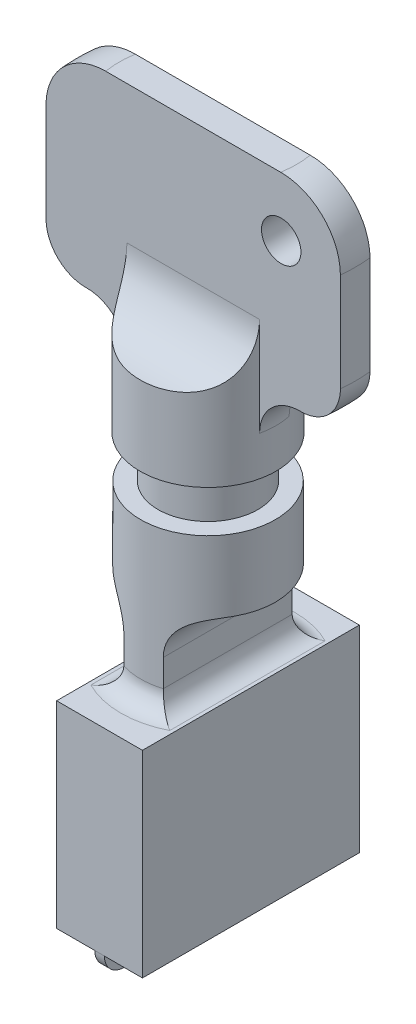
SolidWorks part; units mm, degrees
ref_plane "Front Plane" through (0, 0, 0) normal (0, 0, 1) x (1, 0, 0)
ref_plane "Top Plane" through (0, 0, 0) normal (0, 1, 0) x (1, 0, 0)
ref_plane "Right Plane" through (0, 0, 0) normal (1, 0, 0) x (0, 0, -1)
sketch "Sketch1" plane through (0, 0, 0) normal (0, 0, 1) x (1, 0, 0)
  line L0 (-3.4489, 37.7658) -> (-3.4489, 33.7658)
  line L1 (-3.4489, 33.7658) -> (-2.5348, 33.7658)
  line L2 (-2.5348, 33.7658) -> (-2.5348, 31.625)
  line L3 (-2.5348, 31.625) -> (-3.4177, 31.625)
  line L4 (-3.4177, 31.625) -> (-3.4177, 23)
  line L5 (-3.4177, 23) -> (0, 23)
  line L6 (-3.4489, 37.7658) -> (0, 37.7658)
  line L7 (0, 37.7658) -> (0, 23)
  dimension "D1" = 33.7658
  dimension "D2" = 2.1409
  dimension "D3" = 23
  dimension "D4" = 4
revolve "Revolve1" add sketch "Sketch1" angle 360 about L7
sketch "Sketch2" plane through (0, 37.7658, 0) normal (0, 1, 0) x (1, 0, 0)
  line L1 (-11.4046, 0.75) -> (11.4046, 0.75)
  line L2 (-11.4046, 0.75) -> (-11.4046, -0.75)
  line L3 (-11.4046, -0.75) -> (11.4046, -0.75)
  line L4 (11.4046, 0.75) -> (11.4046, -0.75)
  line L5 (-11.4046, 0.75) -> (11.4046, -0.75) construction
  line L6 (-11.4046, -0.75) -> (11.4046, 0.75) construction
  circle A0 centre (0, 0) radius 3.4489
  circle A1 centre (0, 0) radius 7.5
  circle M3 centre (0, 0) radius 3.4489
  dimension "D2" = 15
  dimension "D1" = 1.5
extrude "Boss-Extrude1" add sketch "Sketch2" along normal blind 10 contours L3 L1 M3 | L1 A1 L3 M3 | L3 A1 L1 M3
fillet "Fillet2" radius 2 2 edges at (7.5, 37.7658, 0) (3.4489, 37.7658, 0)
fillet "Fillet3" radius 3 4 edges at (-7.5, 47.7658, 0) (7.5, 47.7658, 0) (0, 37.7658, -0.75) (0, 37.7658, 0.75)
sketch "Sketch3" plane through (0, 0, 0) normal (0, 0, 1) x (1, 0, 0)
  line L0 (-4.4371, 47.7658) -> (4.4371, 47.7658) construction
  line L1 (7.4624, 44.7658) -> (7.4624, 39.7658) construction
  circle A0 centre (4.4624, 44.7658) radius 1
  dimension "D1" = 2
  dimension "D2" = 3
  dimension "D3" = 3
extrude "Cut-Extrude1" cut sketch "Sketch3" against normal through all and the other way through all
sketch "Sketch4" plane through (0, 0, 0) normal (0, 0, 1) x (1, 0, 0)
  line L1 (-6.5556, 28) -> (-1, 28)
  line L2 (-6.5556, 28) -> (-6.5556, 16.1133)
  line L3 (-6.5556, 16.1133) -> (-1, 16.1133)
  line L4 (-1, 28) -> (-1, 16.1133)
  line L5 (5.8376, 28) -> (1, 28)
  line L6 (5.8376, 28) -> (5.8376, 14.1133)
  line L7 (5.8376, 14.1133) -> (1, 14.1133)
  line L8 (1, 28) -> (1, 14.1133)
  dimension "D1" = 28
  dimension "D2" = 28
  dimension "D3" = 1
  dimension "D4" = 1
extrude "Cut-Extrude2" cut sketch "Sketch4" against normal through all and the other way through all
fillet "Fillet4" radius 2 2 edges at (-1, 28, 0) (1, 28, 0)
sketch "Sketch7" plane through (0, 0, 0) normal (0, 0, 1) x (1, 0, 0)
  line L0 (3.4177, 31.625) -> (-3.4177, 31.625) construction
  line L1 (-2.175, 23.625) -> (2.175, 23.625)
  line L2 (-2.175, 23.625) -> (-2.175, 13.625)
  line L3 (-2.175, 13.625) -> (2.175, 13.625)
  line L4 (2.175, 23.625) -> (2.175, 13.625)
  line L5 (-2.175, 23.625) -> (2.175, 13.625) construction
  line L6 (-2.175, 13.625) -> (2.175, 23.625) construction
  point P0 (0, 18.625)
  dimension "D1" = 4.35
  dimension "D2" = 0
  dimension "D3" = 10
  dimension "D4" = 8
extrude "Boss-Extrude2" add sketch "Sketch7" along normal blind 5.5 and the other way blind 5.5
fillet "Fillet5" radius 1 4 edges at (-1, 23.625, 0) (0, 23.625, -3.4177) (0, 23.625, 3.4177) (1, 23.625, 0)
sketch "Sketch8" plane through (0, 13.625, 0) normal (0, -1, 0) x (1, 0, 0)
  line L0 (-2.175, 5.5) -> (2.175, 5.5) construction
  line L1 (-0.243, -5.5) -> (0.243, -5.5)
  line L2 (-0.243, -5.5) -> (-0.243, 5.5)
  line L3 (-0.243, 5.5) -> (0.243, 5.5)
  line L4 (0.243, -5.5) -> (0.243, 5.5)
  line L5 (-0.243, -5.5) -> (0.243, 5.5) construction
  line L6 (-0.243, 5.5) -> (0.243, -5.5) construction
  point P0 (0, 0)
extrude "Boss-Extrude3" add sketch "Sketch8" along normal blind 1
fillet "Fillet6" radius 1 2 edges at (0, 12.625, -5.5) (0, 12.625, 5.5)
